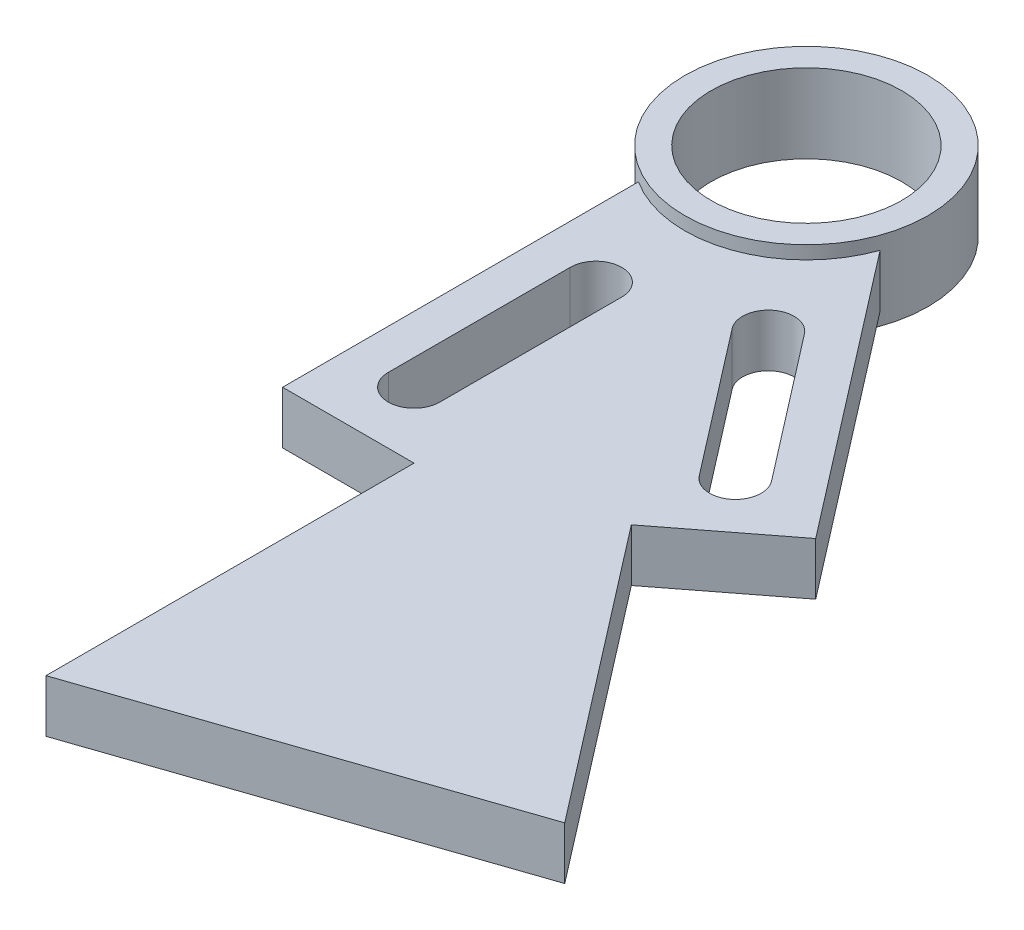
SolidWorks part; units mm, degrees
material "AISI 4130 Steel, normalized at 870C"
ref_plane "Front Plane" through (0, 0, 0) normal (0, 0, 1) x (1, 0, 0)
ref_plane "Top Plane" through (0, 0, 0) normal (0, 1, 0) x (1, 0, 0)
ref_plane "Right Plane" through (0, 0, 0) normal (1, 0, 0) x (0, 0, -1)
sketch "Sketch1" plane through (0, 0, 0) normal (0, 1, 0) x (1, 0, 0)
  line L0 (0, -50.4952) -> (0, -14.6812) construction
  line L1 (30.8439, -39.9802) -> (8.9677, -11.624) construction
  line L2 (0, -47.3837) -> (0, -25.4127) construction
  line L5 (-3.1115, -47.3837) -> (-3.1115, -25.4127)
  line L8 (-7.9375, -55.3212) -> (7.9375, -55.3212)
  line L9 (27.5071, -48.6497) -> (40.0764, -38.9528)
  line L10 (-7.9375, -55.3212) -> (-7.9375, -12.3505)
  line L11 (40.0764, -38.9528) -> (13.8286, -4.9302)
  line L12 (7.9375, -55.3212) -> (7.9375, -99.7712)
  line L13 (27.5071, -48.6497) -> (54.6585, -83.8436)
  line L14 (7.9375, -99.7712) -> (54.6585, -83.8436)
  line L15 (0, -14.6812) -> (0, 0) construction
  line L16 (0, -55.3212) -> (0, -50.4952) construction
  line L17 (33.7918, -43.8013) -> (30.8439, -39.9802)
  line L18 (3.1115, -47.3837) -> (3.1115, -25.4127)
  line L19 (15.5228, -20.1208) -> (28.9433, -37.5167) construction
  line L20 (17.9864, -18.2202) -> (31.4069, -35.6161)
  line L21 (13.0592, -22.0214) -> (26.4797, -39.4173)
  line L22 (8.9677, -11.624) -> (0, 0) construction
  line L23 (0, 0) -> (21.3094, -62.5075) construction
  line L25 (198.9178, -257.8397) -> (14.2221, -18.4349) construction
  line L27 (0, 0) -> (31.298, -91.8074) construction
  circle A0 centre (0, 0) radius 11.5062
  circle A1 centre (0, 0) radius 14.6812
  arc A2 (-3.1115, -47.3837) -> (3.1115, -47.3837) centre (0, -47.3837) ccw
  arc A3 (3.1115, -25.4127) -> (-3.1115, -25.4127) centre (0, -25.4127) ccw
  arc A4 (17.9864, -18.2202) -> (13.0592, -22.0214) centre (15.5228, -20.1208) ccw
  arc A5 (26.4797, -39.4173) -> (31.4069, -35.6161) centre (28.9433, -37.5167) ccw
  point P9 (0, -36.3982)
  point P14 (22.2331, -28.8188)
  point P23 (0, -55.3212)
  point P26 (33.7918, -43.8013)
  point P33 (0, -50.4952)
  point P36 (30.8439, -39.9802)
  point P38 (0, -22.3012)
  dimension "D2" = 29.3624
  dimension "D3" = 40.64
  dimension "D4" = 4.826
  dimension "D6" = 44.45
  dimension "D7" = 7.9375
  dimension "D5" = 4.826
  dimension "D8" = 7.62
  dimension "D9" = 66.04
extrude "Bearing extrude" add sketch "Sketch1" along normal mid plane 9.525 contours A1 A0 region at (-6.8368, 0, -12.521)
extrude "Boss-Extrude2" add sketch "Sketch1<5>" along normal mid plane 6.35 contours A1 L10 L8 L12 L14 L13 L9 L11 A4 A2 region at (19.0286, 0, 55.8173)
sketch "Sketch1<5>" plane through (0, 0, 0) normal (0, 1, 0) x (1, 0, 0) same geometry as "Sketch1"
sketch3d "Tab Point"
  line L0 (21.3094, 0, 62.5075) -> (21.3094, 22.225, 62.5075) construction
  line L1 (0, 0, 0) -> (21.3094, 0, 62.5075) construction
  line L2 (0, 0, 0) -> (31.298, 0, 91.8074) construction
  dimension "D1" = 22.225
equation "\"Apex_thickness\"= .25"
equation "\"Bearing_diameter\"= .906"
equation "\"A-arm_angle\"= 32.91"
equation "\"D1@Sketch1\"=\"Bearing_diameter\""
equation "\"D1@Boss-Extrude2\"= \"Apex_thickness\""
equation "\"apex slot\"= 1.4"
equation "\"tube diameter\"= 5 / 8"
